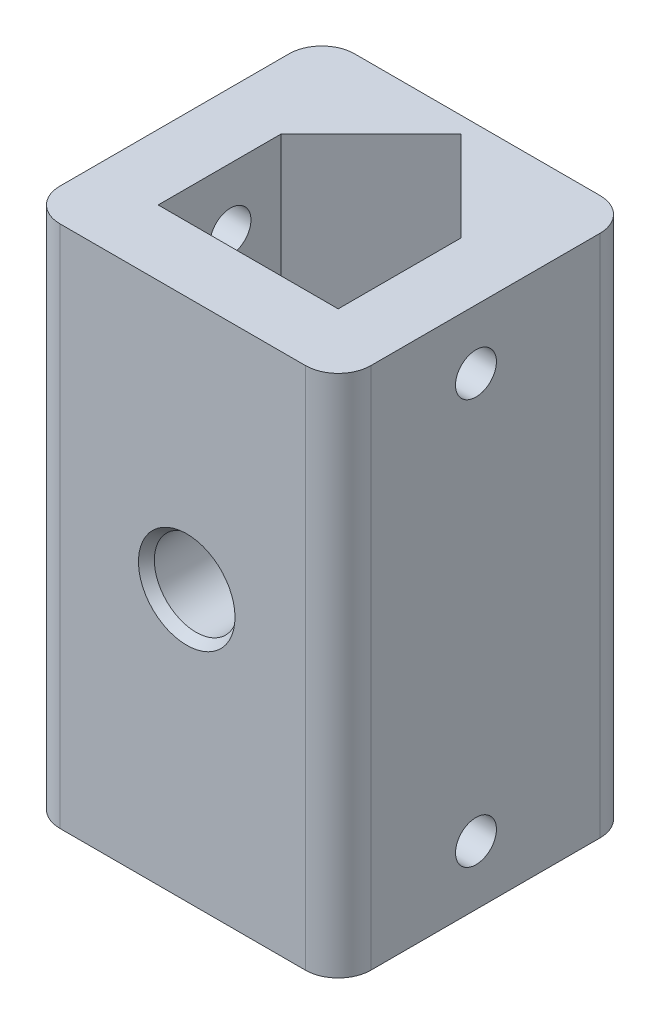
SolidWorks part; units mm, degrees
ref_plane "Front Plane" through (0, 0, 0) normal (0, 0, 1) x (1, 0, 0)
ref_plane "Top Plane" through (0, 0, 0) normal (0, 1, 0) x (1, 0, 0)
ref_plane "Right Plane" through (0, 0, 0) normal (1, 0, 0) x (0, 0, -1)
sketch "Sketch1" plane through (0, 0, 0) normal (0, 1, 0) x (1, 0, 0)
  line L0 (4, 4) -> (15, 4)
  line L1 (0, 0) -> (19, 0)
  line L2 (0, 0) -> (0, 18)
  line L3 (0, 18) -> (19, 18)
  line L4 (19, 0) -> (19, 18)
  line L5 (15, 4) -> (15, 11.5)
  line L6 (15, 11.5) -> (9.5, 17)
  line L7 (9.5, 17) -> (4, 11.5)
  line L8 (4, 11.5) -> (4, 4)
  circle A0 centre (9.5, 8.6887) radius 5 construction
  point P12 (8, 9.3714)
  point P13 (7.5155, 7.8843)
  point P14 (8, 8.0738)
  point P15 (8, 8.7097)
  point P16 (9.5, 8.6887)
  dimension "D10" = 10
  dimension "D1" = 19
  dimension "D2" = 18
  dimension "D3" = 90
  dimension "D4" = 9.5
  dimension "D5" = 11
  dimension "D6" = 4
  dimension "D7" = 7.5
  dimension "D8" = 7.5
  dimension "D9" = 4
extrude "Boss-Extrude1" add sketch "Sketch1" along normal blind 32
hole_wizard "Tap Drill for M3x0.5 Tap1" positions "Sketch2" profile "Sketch3" hole size "M3x0.5" standard "ANSI Metric" end condition through all
sketch "Sketch2" plane through (19, 0, 0) normal (1, 0, 0) x (0, 0, -1)
  point P0 (8.4192, 28.375)
  point P3 (8.4192, 3.625)
sketch "Sketch3" plane through (19, 28.375, -8.4192) normal (0, 1, 0) x (0, 0, -1)
  line L0 (0, 0) -> (0, 19)
  line L1 (0, 19) -> (1.25, 19)
  line L2 (1.25, 19) -> (1.25, 0)
  line L5 (1.25, 0) -> (0, 0)
  line L11 (0, -6.35) -> (0, 107.95) construction
  dimension "Thru Hole Dia." = 2.5
  dimension "Thru Hole Depth" = 19
fillet "Fillet1" radius 2 4 edges at (19, 16, -18) (19, 16, 0) (0, 16, -18) (0, 16, 0)
hole_wizard "M5 Clearance Hole1" positions "Sketch4" profile "Sketch5" hole size "M5" standard "ANSI Metric" end condition up to next
sketch "Sketch4" plane through (0, 0, 0) normal (0, 0, 1) x (1, 0, 0)
  point P0 (9.7444, 16.5211)
sketch "Sketch5" plane through (9.7444, 16.5211, 0) normal (1, 0, 0) x (0, -1, 0)
  line L0 (0, 0) -> (0, 4)
  line L1 (0, 4) -> (2.55, 4)
  line L2 (2.55, 4) -> (2.55, 0.5713)
  line L3 (2.55, 0.5713) -> (2.95, 0)
  line L5 (2.95, 0) -> (0, 0)
  line L6 (-2.55, 0.5713) -> (-2.95, 0) construction
  line L11 (0, -6.35) -> (0, 107.95) construction
  dimension "Thru Hole Dia." = 5.1
  dimension "Thru Hole Depth" = 4
  dimension "Near C'Sink Dia." = 5.9
  dimension "Near C'Sink Angle" = 70
